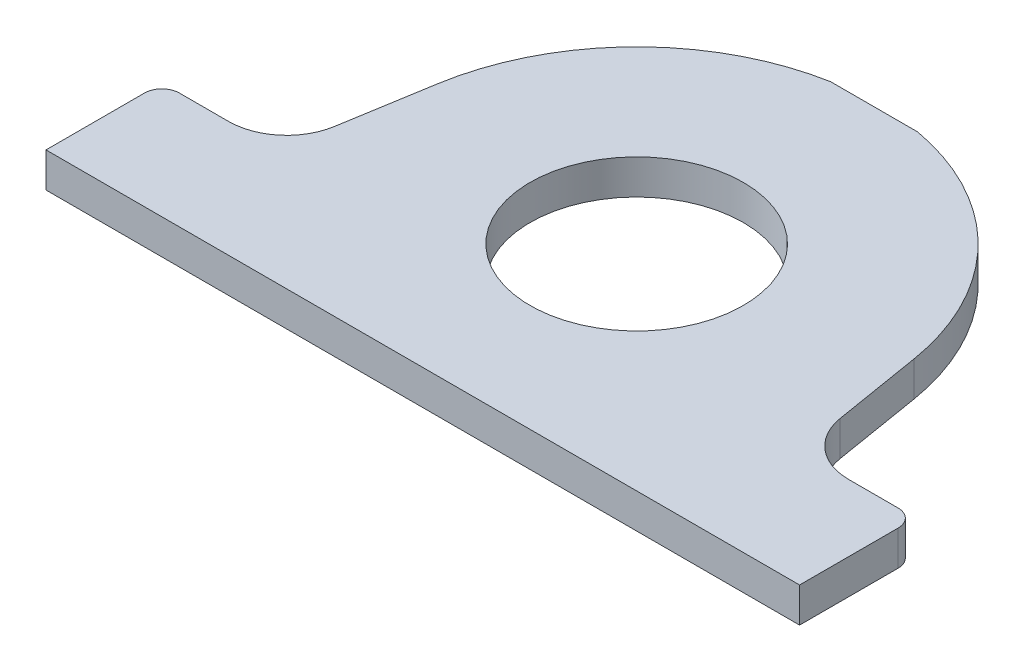
SolidWorks part; units mm, degrees
material "Acrylic (Medium-high impact)"
ref_plane "Front Plane" through (0, 0, 0) normal (0, 0, 1) x (1, 0, 0)
ref_plane "Top Plane" through (0, 0, 0) normal (0, 1, 0) x (1, 0, 0)
ref_plane "Right Plane" through (0, 0, 0) normal (1, 0, 0) x (0, 0, -1)
sketch "Sketch1" plane through (0, 0, 0) normal (0, 1, 0) x (1, 0, 0)
  line L0 (-41.0948, 6.7778) -> (-45, -16.9)
  line L1 (-65, -16.9) -> (-45, -16.9)
  line L3 (-65, -36.9) -> (65, -36.9)
  line L5 (41.0948, 6.7778) -> (45, -16.9)
  line L6 (0, -20.9) -> (0, -36.9) construction
  line L7 (45, -16.9) -> (65, -16.9)
  line L10 (65, -16.9) -> (65, -36.9)
  line L11 (-65, -16.9) -> (-65, -36.9)
  circle A0 centre (0, 0) radius 20.9
  arc A1 (41.0948, 6.7778) -> (-41.0948, 6.7778) centre (0, 0) ccw
  circle A3 centre (0, 0) radius 41.65 construction
  point P11 (27.5, 0)
  dimension "D1" = 41.8
  dimension "D3" = 16
  dimension "D4" = 130
  dimension "D5" = 20
  dimension "D6" = 20
  dimension "D2" = 20.75
extrude "Boss-Extrude1" add sketch "Sketch1" along normal blind 30
sketch "Sketch2" plane through (0, 0, 16.9) normal (0, 0, -1) x (-1, 0, 0)
  line L0 (-65, 30) -> (-45, 0) construction
  circle A0 centre (-55, 15) radius 1
  dimension "D1" = 2
extrude "Cut-Extrude1" cut sketch "Sketch2" against normal blind 3
sketch "Sketch3" plane through (0, 0, 16.9) normal (0, 0, -1) x (-1, 0, 0)
  line L0 (45, 30) -> (65, 0) construction
  circle A0 centre (55, 15) radius 1
  dimension "D1" = 2
extrude "Cut-Extrude2" cut sketch "Sketch3" against normal blind 3
sketch "Sketch4" plane through (0, 0, 0) normal (0, -1, 0) x (1, 0, 0)
  line L1 (7.5, -44.9579) -> (-7.5, -44.9579)
  line L2 (7.5, -44.9579) -> (7.5, -40.9692)
  line L3 (7.5, -40.9692) -> (-7.5, -40.9692)
  line L4 (-7.5, -44.9579) -> (-7.5, -40.9692)
  line L5 (7.5, -44.9579) -> (-7.5, -40.9692) construction
  line L6 (7.5, -40.9692) -> (-7.5, -44.9579) construction
  arc A1 (-41.0948, -6.7778) -> (41.0948, -6.7778) centre (0, 0) ccw construction
  point P0 (0, -42.9635)
  dimension "D1" = 15
sketch "Sketch6" plane through (0, 0, 0) normal (0, -1, 0) x (1, 0, 0)
  circle A0 centre (0, 0) radius 22.9
  circle A1 centre (0, 0) radius 20.9 construction
  circle A2 centre (0, 0) radius 18.4
  dimension "D1" = 2
  dimension "D2" = 4.5
extrude "Boss-Extrude2" add sketch "Sketch6" against normal blind 12
fillet "Fillet1" radius 10 2 edges at (45, 15, 16.9) (-45, 15, 16.9)
chamfer "Chamfer1" distance 2 angle 45 1 edges at (0, 30, 20.9)
extrude "Cut-Extrude3" cut sketch "Sketch4" against normal through all
sketch "Sketch8" plane through (0, 0, -40.9692) normal (0, 0, -1) x (-1, 0, 0)
  line L0 (-7.5, 30) -> (7.5, 14) construction
  line L1 (7.5, 30) -> (7.5, 0) construction
  circle A0 centre (0, 22) radius 1
  dimension "D2" = 2
  dimension "D1" = 16
extrude "Cut-Extrude4" cut sketch "Sketch8" against normal blind 2
fillet "Fillet2" radius 3 7 edges at (59.2429, 30, 16.9) (47.0156, 30, 14.5247) (42.357, 30, 0.8748) (-59.2429, 30, 16.9) (-47.0156, 30, 14.5247) (-42.357, 30, 0.8748) (-29.709, 30, -29.1907)
fillet "Fillet3" radius 3 6 edges at (65, 30, 28.4) (65, 29.1213, 17.7787) (-65, 30, 28.4) (-65, 29.1213, 17.7787) (65, 13.5, 16.9) (-65, 13.5, 16.9)
sketch "Sketch9" plane through (0, 0, 36.9) normal (0, 0, 1) x (1, 0, 0)
  line L0 (-65, 0) -> (65, 0) construction
  line L1 (-76.9076, 34.2757) -> (87.1018, 34.2757)
  line L2 (-76.9076, 34.2757) -> (-76.9076, 6)
  line L3 (-76.9076, 6) -> (87.1018, 6)
  line L4 (87.1018, 34.2757) -> (87.1018, 6)
  dimension "D1" = 6
extrude "Cut-Extrude5" cut sketch "Sketch9" against normal blind 93
